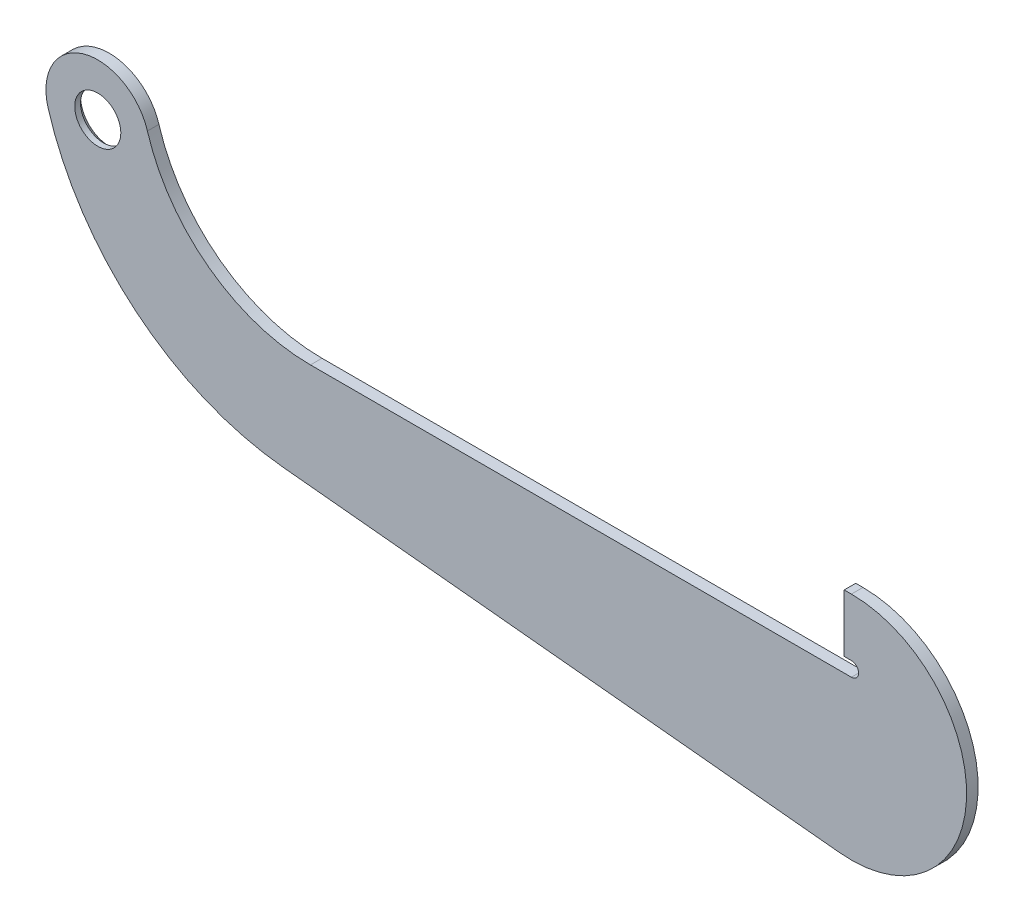
SolidWorks part; units mm, degrees
material "AISI 1020"
ref_plane "Спереди" through (0, 0, 0) normal (0, 0, 1) x (1, 0, 0)
ref_plane "Сверху" through (0, 0, 0) normal (0, 1, 0) x (1, 0, 0)
ref_plane "Справа" through (0, 0, 0) normal (1, 0, 0) x (0, 0, -1)
sketch "Эскиз1" plane through (0, 0, 0) normal (0, 0, 1) x (1, 0, 0)
  line L0 (259.1533, -31.815) -> (253.1533, -31.815) construction
  line L1 (259.1533, -7.3541) -> (259.1533, -31.815) construction
  line L2 (259.1533, -11.815) -> (261.6533, -11.815)
  line L3 (259.1533, -11.815) -> (259.1533, -31.815)
  line L4 (259.1533, -31.815) -> (261.6533, -31.815)
  line L5 (261.6533, -36.815) -> (73.8382, -36.815)
  line L6 (257.6846, -91.6176) -> (64.3989, -72.3455)
  line L7 (153.1533, 46.3042) -> (0, 0) construction
  line L8 (261.6533, -11.815) -> (261.6533, -51.815) construction
  circle A0 centre (0, 0) radius 8 construction
  circle A1 centre (0, 0) radius 8
  arc A2 (17.2297, 5.2092) -> (-17.2297, -5.2092) centre (0, 0) ccw
  arc A3 (-5.4242, 17.1633) -> (4.9934, -17.2935) centre (0, 0) ccw construction
  arc A4 (261.6533, -36.815) -> (261.6533, -31.815) centre (261.6533, -34.315) ccw
  arc A6 (73.8382, -36.815) -> (17.2297, 5.2092) centre (73.8382, 22.3242) cw
  arc A9 (-17.2297, -5.2092) -> (64.3989, -72.3455) centre (73.8382, 22.3242) ccw
  arc A11 (257.6846, -91.6176) -> (261.6533, -11.815) centre (261.6533, -51.815) ccw
  point P23 (261.6533, -31.815)
  point P32 (253.1533, -11.815)
  dimension "D1" = 5
base flange "Базовая кромка1" sketch "Эскиз1" thickness 4 reverse thickness direction yes parameters "D1"=0.74
chamfer "Фаска1" [suppressed] distance 2 angle 45
chamfer "Фаска2" distance 2 angle 45 1 edges at (8, 0, 0)
sketch "Сгиб-Линии1" [suppressed] plane through (0, 0, 0) normal (0, 1, 0) x (1, 0, 0)
sketch "Граничная рамка1" [suppressed] plane through (0, 0, 0) normal (0, 1, 0) x (1, 0, 0)
sheet metal parameters "Листовой металл3" thickness 4 parameters "D1"=0.74
flat pattern "Развертка3" [suppressed]
sketch "Сгиб-Линии2" plane through (0, 0, 0) normal (0, 1, 0) x (1, 0, 0)
sketch3d "Граничная рамка2" [suppressed]
  line L0 (277.5102, 54.2286, 0) -> (-44.2527, 17.7377, 0) construction
  line L1 (286.8223, -27.8815, 0) -> (-34.9406, -64.3724, 0) construction
  line L2 (277.5102, 54.2286, 0) -> (286.8223, -27.8815, 0) construction
  line L3 (-44.2527, 17.7377, 0) -> (-34.9406, -64.3724, 0) construction
